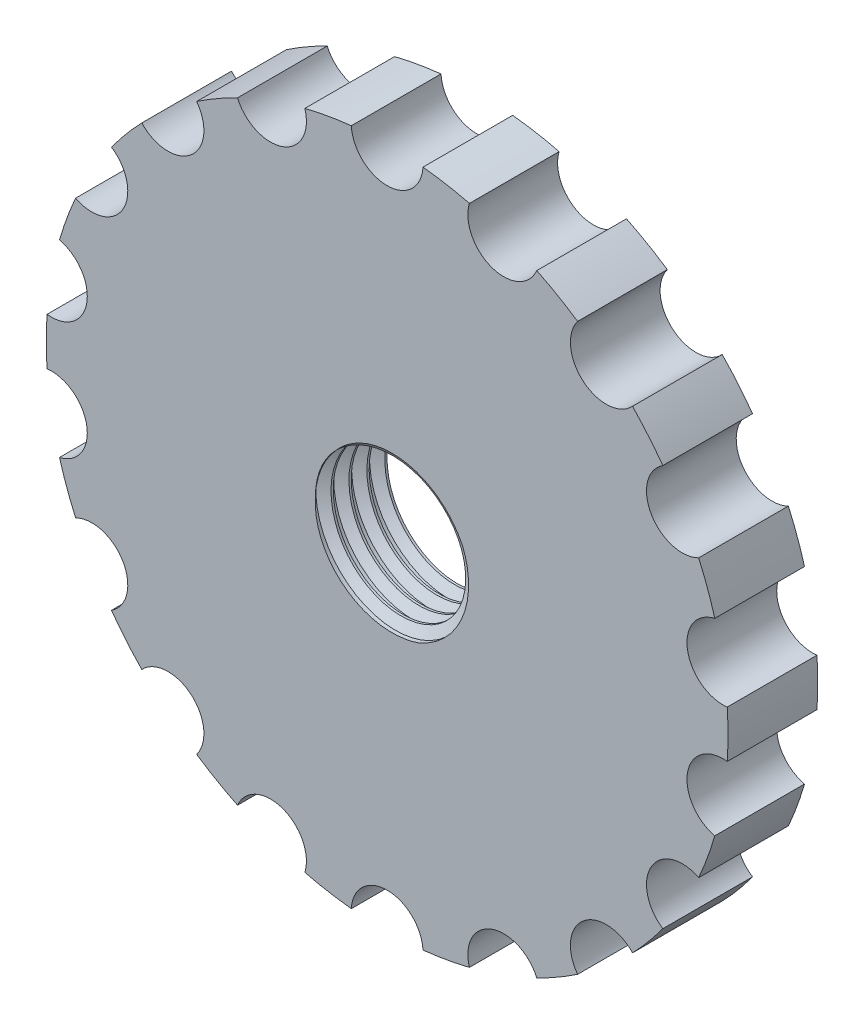
SolidWorks part; units mm, degrees
ref_plane "Front" through (0, 0, 0) normal (0, 0, 1) x (1, 0, 0)
ref_plane "Top" through (0, 0, 0) normal (0, 1, 0) x (1, 0, 0)
ref_plane "Right" through (0, 0, 0) normal (1, 0, 0) x (0, 0, -1)
sketch "Sketch1" plane through (0, 0, 0) normal (0, 0, 1) x (1, 0, 0)
  circle A0 centre (0, 0) radius 19
extrude "Boss-Extrude1" add sketch "Sketch1" along normal blind 5
sketch "Sketch5" plane through (0, 0, 5) normal (0, 0, 1) x (1, 0, 0)
  line L0 (0, 0) -> (0, 25.2091) construction
  circle A21 centre (0, 0) radius 19 construction
  circle A22 centre (0, 19) radius 2
  circle A23 centre (6.4984, 17.8542) radius 2
  circle A24 centre (12.213, 14.5548) radius 2
  circle A25 centre (16.4545, 9.5) radius 2
  circle A26 centre (18.7113, 3.2993) radius 2
  circle A27 centre (18.7113, -3.2993) radius 2
  circle A28 centre (16.4545, -9.5) radius 2
  circle A29 centre (12.213, -14.5548) radius 2
  circle A30 centre (6.4984, -17.8542) radius 2
  circle A31 centre (0, -19) radius 2
  circle A32 centre (-6.4984, -17.8542) radius 2
  circle A33 centre (-12.213, -14.5548) radius 2
  circle A34 centre (-16.4545, -9.5) radius 2
  circle A35 centre (-18.7113, -3.2993) radius 2
  circle A36 centre (-18.7113, 3.2993) radius 2
  circle A37 centre (-16.4545, 9.5) radius 2
  circle A38 centre (-12.213, 14.5548) radius 2
  circle A39 centre (-6.4984, 17.8542) radius 2
  point P42 (0, 0)
extrude "Cut-Extrude2" cut sketch "Sketch5" against normal blind 10
sketch "Sketch7" plane through (0, 0, 0) normal (0, 0, -1) x (-1, 0, 0)
  circle A0 centre (0, 0) radius 4
extrude "Cut-Extrude3" cut sketch "Sketch7" against normal through all both and the other way through all
sketch "Sketch8" plane through (0, 0, 0) normal (0, 0, -1) x (-1, 0, 0)
  circle A0 centre (0, 0) radius 7.6
extrude "Cut-Extrude4" cut sketch "Sketch8" against normal blind 1
thread "Thread1" pitch 1 method cut profile "Thread Profile1" start angle 0, offset 2, length 10, pitch 1, diameter 8
ref_plane "Plane1" through (-4, 0, 7) normal (0, 1, 0) x (1, 0, 0)
sketch "Thread Profile1" plane through (-4, 0, 7) normal (0, 1, 0) x (1, 0, 0)
  line L0 (0, 0) -> (0, 1) construction
  line L11 (0, 0) -> (0, 0.875)
  line L12 (0, 0.875) -> (-0.5413, 0.5625)
  line L13 (-0.5413, 0.5625) -> (-0.5413, 0.3125)
  line L15 (-0.5413, 0.3125) -> (0, 0)
  line L17 (-0.5413, 0.4375) -> (0, 0.4375) construction
  point P2 (0, 0)
  dimension "Pitch" = 1
  dimension "Profile_Angle" = 60
  dimension "Profile_Land" = 0.25
  dimension "Profile_Height" = 0.5413
